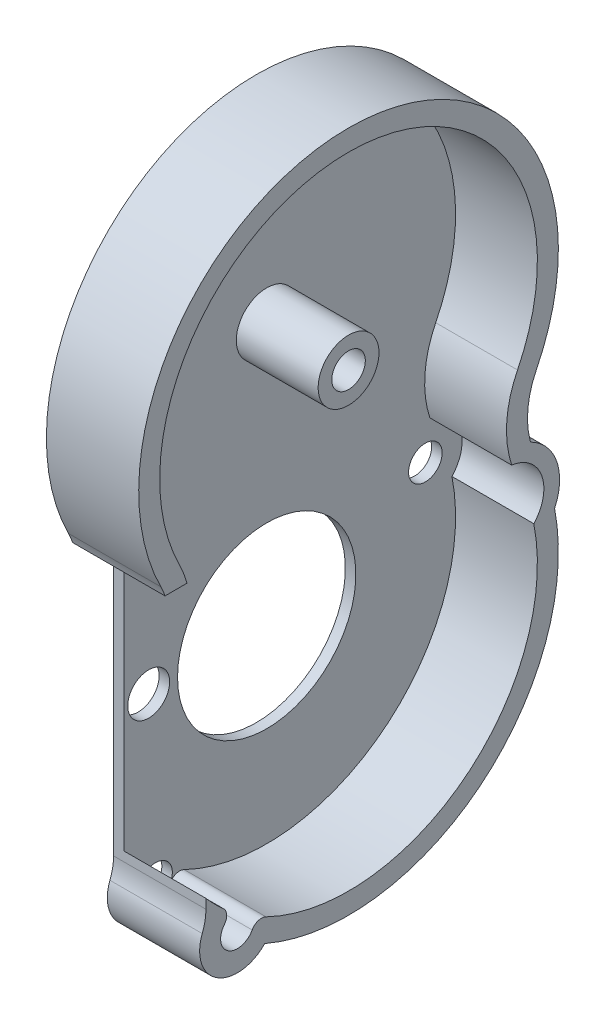
SolidWorks part; units mm, degrees
ref_plane "Front Plane" through (0, 0, 0) normal (0, 0, 1) x (1, 0, 0)
ref_plane "Top Plane" through (0, 0, 0) normal (0, 1, 0) x (1, 0, 0)
ref_plane "Right Plane" through (0, 0, 0) normal (1, 0, 0) x (0, 0, -1)
sketch "Sketch1" plane through (-9277.0205, 0, 0) normal (1, 0, 0) x (0, 0, -1)
  line L0 (-5181.361, -2713.1295) -> (-5181.361, -2685.3176)
  line L1 (-5181.361, -2713.1295) -> (-5181.361, -2689.5176) construction
  line L3 (-5181.361, -2685.3176) -> (-5185.2604, -2685.3176)
  line L4 (-5193.846, -2689.3176) -> (-5161.846, -2689.3176) construction
  line L5 (-5172.761, -2713.6855) -> (-5162.046, -2713.6855) construction
  line L6 (-5172.761, -2713.6855) -> (-5162.046, -2713.6855)
  line L7 (-5174.761, -2716.2855) -> (-5174.761, -2715.6855) construction
  line L8 (-5174.761, -2716.2855) -> (-5174.761, -2715.6855)
  circle A0 centre (-5167.766, -2700.4326) radius 4.175 construction
  circle A1 centre (-5179.016, -2700.4326) radius 1.995 construction
  arc A2 (-5152.5846, -2689.5179) -> (-5152.646, -2689.5176) centre (-5152.646, -2694.5176) ccw
  circle A3 centre (-5178.361, -2716.2855) radius 1.6 construction
  circle A4 centre (-5167.766, -2700.4326) radius 4.175
  circle A5 centre (-5179.016, -2700.4326) radius 1.995
  circle A7 centre (-5178.361, -2716.2855) radius 1.6
  arc A8 (-5183.8728, -2692.3969) -> (-5150.1101, -2696.9299) centre (-5167.766, -2700.4326) ccw
  arc A9 (-5151.6593, -2683.4683) -> (-5183.8728, -2683.4683) centre (-5167.766, -2675.4326) ccw
  arc A10 (-5152.2146, -2691.0443) -> (-5151.6593, -2683.4683) centre (-5142.7111, -2687.9326) cw
  arc A11 (-5183.8728, -2692.3969) -> (-5183.8728, -2683.4683) centre (-5192.821, -2687.9326) ccw
  arc A12 (-5149.8696, -2684.3611) -> (-5185.6624, -2684.3611) centre (-5167.766, -2675.4326) ccw
  arc A13 (-5185.6624, -2691.504) -> (-5185.6624, -2684.3611) centre (-5192.821, -2687.9326) ccw
  arc A14 (-5185.6624, -2691.504) -> (-5148.126, -2696.6552) centre (-5167.766, -2700.4326) ccw
  arc A15 (-5150.4297, -2690.0356) -> (-5149.8696, -2684.3611) centre (-5142.7111, -2687.9326) cw
  circle A16 centre (-5167.766, -2675.4326) radius 2.9
  circle A17 centre (-5167.766, -2700.4326) radius 8.499
  circle A18 centre (-5167.766, -2700.4326) radius 7.499 construction
  circle A19 centre (-5152.646, -2694.5176) radius 1.6 construction
  circle A20 centre (-5152.646, -2694.5176) radius 1.6
  arc A21 (-5151.846, -2699.4532) -> (-5152.646, -2689.5176) centre (-5152.646, -2694.5176) ccw construction
  arc A22 (-5148.126, -2696.6552) -> (-5150.4297, -2690.0356) centre (-5152.646, -2694.5176) ccw
  arc A23 (-5185.6624, -2691.504) -> (-5149.8696, -2691.504) centre (-5167.766, -2700.4326) ccw construction
  arc A24 (-5149.8696, -2691.504) -> (-5149.8696, -2684.3611) centre (-5142.7111, -2687.9326) cw construction
  arc A25 (-5152.2146, -2691.0443) -> (-5150.1101, -2696.9299) centre (-5152.646, -2694.5176) cw
  arc A27 (-5183.8728, -2692.3969) -> (-5151.6593, -2692.3969) centre (-5167.766, -2700.4326) ccw construction
  arc A28 (-5151.6593, -2692.3969) -> (-5151.6593, -2683.4683) centre (-5142.7111, -2687.9326) cw construction
  arc A29 (-5181.7099, -2714.9644) -> (-5181.361, -2713.1295) centre (-5186.361, -2713.1295) ccw construction
  arc A30 (-5181.7099, -2714.9644) -> (-5181.361, -2713.1295) centre (-5186.361, -2713.1295) ccw
  arc A31 (-5172.761, -2713.6855) -> (-5174.761, -2715.6855) centre (-5172.761, -2715.6855) ccw construction
  circle A32 centre (-5167.766, -2675.4326) radius 1.6
  arc A33 (-5181.7099, -2714.9644) -> (-5174.761, -2716.2855) centre (-5178.361, -2716.2855) ccw construction
  arc A34 (-5172.761, -2713.6855) -> (-5174.761, -2715.6855) centre (-5172.761, -2715.6855) ccw
  arc A35 (-5181.7099, -2714.9644) -> (-5174.761, -2716.2855) centre (-5178.361, -2716.2855) ccw
  circle M47 centre (-5178.361, -2716.2855) radius 1.6
  line M48 (-5156.646, -2704.0154) -> (-5156.646, -2706.4855)
  arc M49 (-5156.646, -2706.4855) -> (-5161.846, -2711.6855) centre (-5161.846, -2706.4855) cw
  line M50 (-5161.846, -2711.6855) -> (-5181.361, -2711.6855)
  line M51 (-5181.361, -2711.6855) -> (-5181.361, -2713.1295)
  line M53 (-5172.761, -2713.6855) -> (-5162.046, -2713.6855)
  arc M54 (-5162.046, -2713.6855) -> (-5152.046, -2703.6855) centre (-5162.046, -2703.6855) ccw
  line M55 (-5152.046, -2703.6855) -> (-5152.046, -2703.1326)
  line M56 (-5152.046, -2703.1326) -> (-5155.7632, -2703.1326)
  line M57 (-5155.7632, -2703.1326) -> (-5156.646, -2704.0154)
  arc M79 (-5181.7099, -2714.9644) -> (-5174.761, -2716.2855) centre (-5178.361, -2716.2855) ccw
  line M80 (-5174.761, -2716.2855) -> (-5174.761, -2715.6855)
  arc M81 (-5174.761, -2715.6855) -> (-5172.761, -2713.6855) centre (-5172.761, -2715.6855) cw
  dimension "D1" = 10
  dimension "D2" = 18
  dimension "D5" = 5.8
  dimension "D6" = 1
  dimension "D7" = 3.5
  dimension "D8" = 4
  dimension "D9" = 3.2
  dimension "D4" = 25
  dimension "D3" = 2
extrude "Boss-Extrude1" add sketch "Sketch1" along normal offset from surface (8.8 mm away) 0.5 contours A14 A7 A8 M51 M50 | A14 L0 M79 M47 | A7 A14 A8 M79 | A10 A25 A8 A14 A22 A15 A12 A13 L3 A11 A9 M79 region at (-9277.0205, -2714.4181, 5180.4652) region at (-9277.0205, -2684.5537, 5184.2147) region at (-9277.0205, -2717.9956, 5179.504) region at (-9277.0205, -2717.4802, 5176.1433) offset beyond the face yes
extrude "Boss-Extrude2" add sketch "Sketch1<3>" along normal offset from surface (1 mm away) 0.3 contours A8 M50 M47 M79 M80 M81 M53 M54 M55 M56 M57 M48 M49 | A25 A10 A9 A11 L3 L0 A8 A5 A16 A17 A20 M50 M49 M48 M57 M56 M55 M54 M53 M81 M80 M79 region at (-9277.0205, -2712.0097, 5171.6035) region at (-9277.0205, -2683.9386, 5167.0055)
sketch "Sketch1<3>" plane through (-9277.0205, 0, 0) normal (1, 0, 0) x (0, 0, -1) same geometry as "Sketch1"
extrude "Boss-Extrude3" add sketch "Sketch1<4>" along normal up to surface (8.8 mm away) contours A16 region at (-9277.0205, -2675.4326, 5170.584) up to face at (-9268.2205, -2696.0184, 5169.0199)
sketch "Sketch1<4>" plane through (-9277.0205, 0, 0) normal (1, 0, 0) x (0, 0, -1) same geometry as "Sketch1"
fillet "Fillet1" radius 1 2 edges at (-9272.1205, -2716.0101, 5176.7849) (-9272.1205, -2714.7239, 5178.7094)
